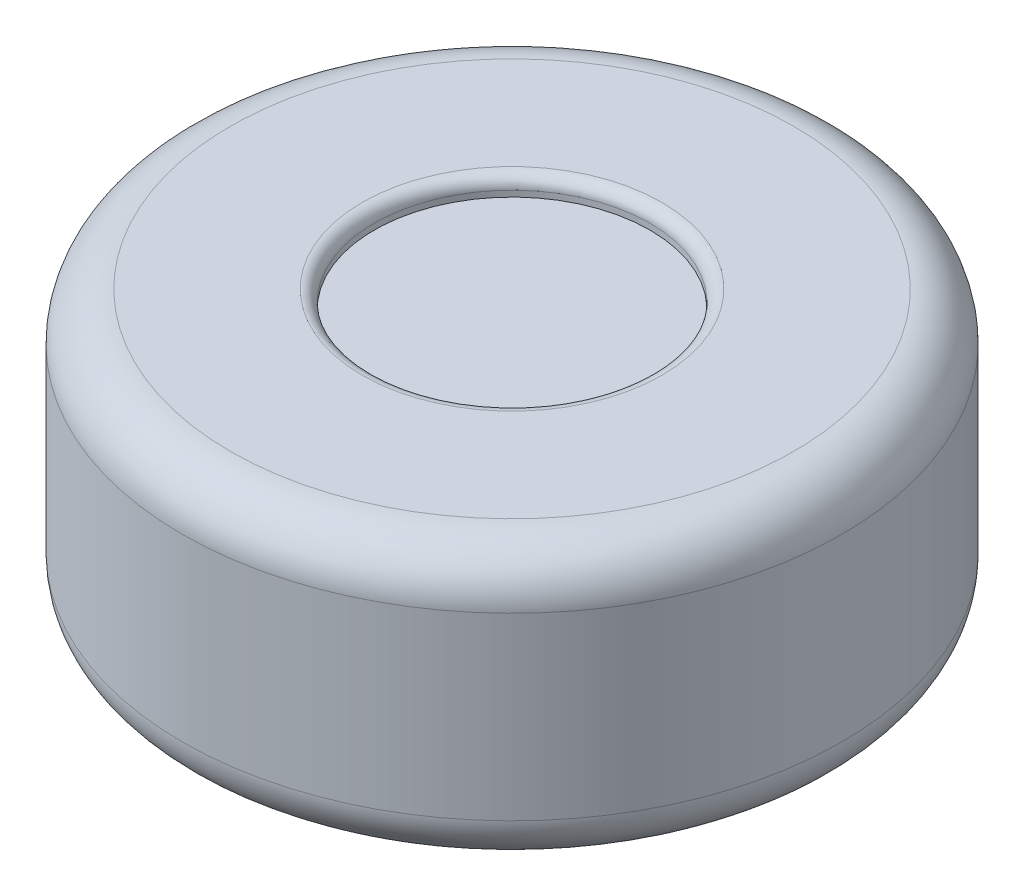
SolidWorks part; units mm, degrees
ref_plane "Alzado" through (0, 0, 0) normal (0, 0, 1) x (1, 0, 0)
ref_plane "Planta" through (0, 0, 0) normal (0, 1, 0) x (1, 0, 0)
ref_plane "Vista lateral" through (0, 0, 0) normal (1, 0, 0) x (0, 0, -1)
sketch "Croquis1" plane through (0, 0, 0) normal (0, 1, 0) x (1, 0, 0)
  circle A0 centre (0, 0) radius 120
  dimension "D1" = 240
extrude "Saliente-Extruir1" add sketch "Croquis1" along normal blind 100 and the other way blind 100
sketch "Croquis3" plane through (0, 0, 0) normal (0, 1, 0) x (1, 0, 0)
  circle A0 centre (0, 0) radius 275
  circle A1 centre (0, 0) radius 115
  dimension "D1" = 550
  dimension "D2" = 0
  dimension "D3" = 230
extrude "Saliente-Extruir4" add sketch "Croquis3" along normal blind 115 and the other way blind 115
fillet "Redondeo1" radius 40 2 edges at (0, 115, 275) (0, -115, 275)
fillet "Redondeo2" radius 10 1 edges at (0, -115, 115)
fillet "Redondeo3" radius 10 1 edges at (0, 115, 115)
